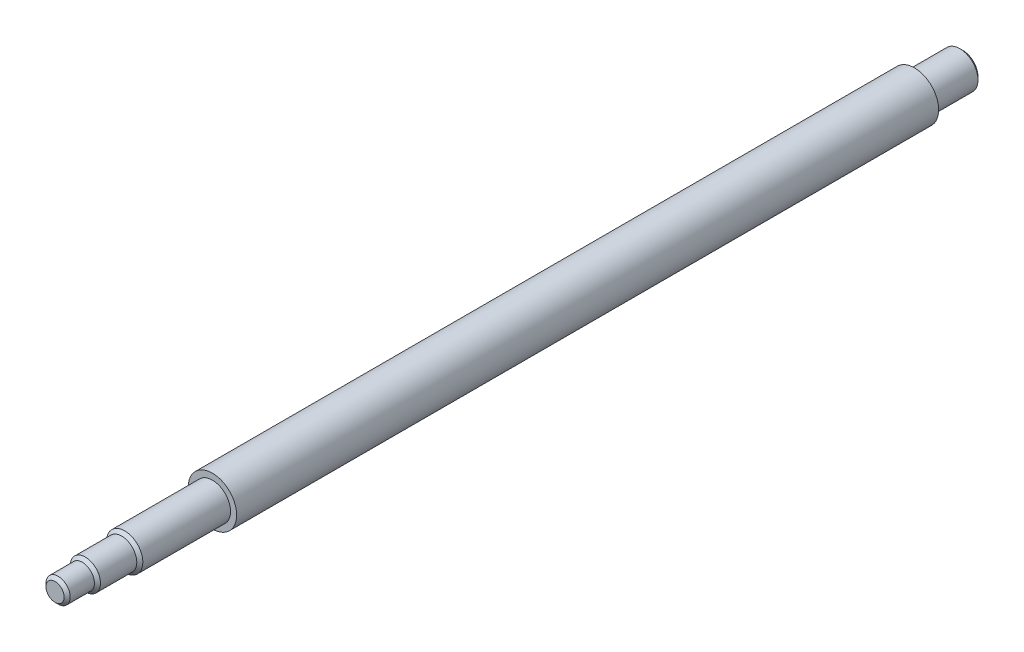
SolidWorks part; units mm, degrees
material "1.0037 (S235JR)"
ref_plane "Płaszczyzna przednia" through (0, 0, 0) normal (0, 0, 1) x (1, 0, 0)
ref_plane "Płaszczyzna górna" through (0, 0, 0) normal (0, 1, 0) x (1, 0, 0)
ref_plane "Płaszczyzna prawa" through (0, 0, 0) normal (1, 0, 0) x (0, 0, -1)
sketch "Szkic1" plane through (0, 0, 0) normal (1, 0, 0) x (0, 0, -1)
  line L0 (0, 0) -> (300, 0)
  line L1 (300, 0) -> (300, 6)
  line L2 (300, 6) -> (284, 6)
  line L3 (284, 6) -> (284, 8)
  line L4 (284, 8) -> (52, 8)
  line L5 (52, 8) -> (52, 6)
  line L6 (52, 6) -> (22, 6)
  line L7 (22, 6) -> (22, 5)
  line L8 (22, 5) -> (9, 5)
  line L9 (0, 4) -> (0, 0)
  line L10 (0, 4) -> (9, 4)
  line L11 (9, 4) -> (9, 5)
  dimension "D1" = 300
  dimension "D2" = 6
  dimension "D3" = 5
  dimension "D4" = 6
  dimension "D5" = 8
  dimension "D6" = 16
  dimension "D7" = 30
  dimension "D8" = 13
  dimension "D9" = 9
  dimension "D10" = 4
revolve "Obrót1" add sketch "Szkic1" angle 360 about L0
chamfer "Sfazowanie1" distance 1 angle 45 3 edges at (4, 0, 0) (5, 0, -9) (6, 0, -22)
chamfer "Sfazowanie2" distance 1 angle 45 1 edges at (6, 0, -300)
